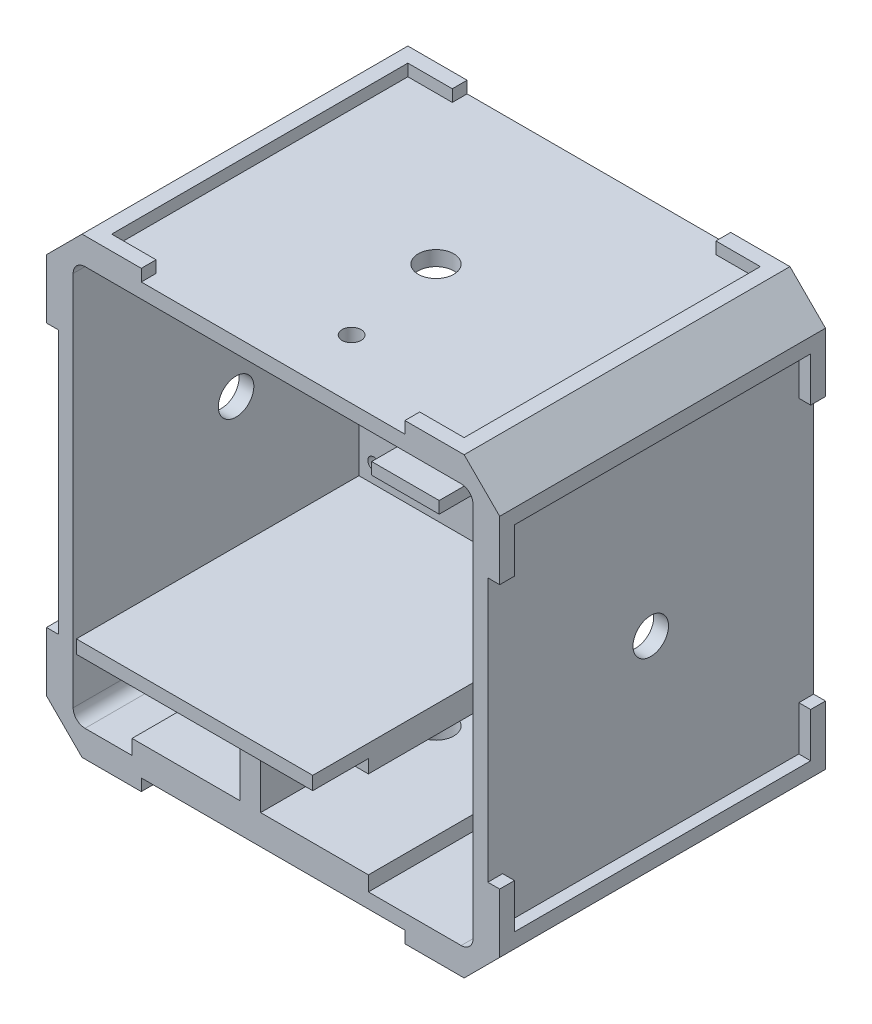
SolidWorks part; units mm, degrees
ref_plane "Front Plane" through (0, 0, 0) normal (0, 0, 1) x (1, 0, 0)
ref_plane "Top Plane" through (0, 0, 0) normal (0, 1, 0) x (1, 0, 0)
ref_plane "Right Plane" through (0, 0, 0) normal (1, 0, 0) x (0, 0, -1)
sketch "Sketch1" plane through (0, 0, 0) normal (0, 0, 1) x (1, 0, 0)
  line L0 (-33.75, -33.75) -> (33.75, -33.75) construction
  line L1 (-31.75, 33.75) -> (31.75, 33.75)
  line L2 (-33.75, 31.75) -> (-33.75, -31.75)
  line L3 (-31.75, -33.75) -> (31.75, -33.75)
  line L4 (33.75, 31.75) -> (33.75, -31.75)
  line L5 (-36.25, 32.25) -> (-36.25, -32.25)
  line L6 (33.75, 33.75) -> (33.75, -33.75) construction
  line L7 (-32.25, -36.25) -> (32.25, -36.25)
  line L8 (36.25, 32.25) -> (36.25, -32.25)
  line L9 (-32.25, 36.25) -> (32.25, 36.25)
  line L10 (-36.25, 36.25) -> (-36.25, -36.25) construction
  line L11 (-36.25, 36.25) -> (36.25, 36.25) construction
  line L12 (-33.75, 33.75) -> (33.75, 33.75) construction
  line L13 (-33.75, 33.75) -> (-33.75, -33.75) construction
  line L14 (-36.25, -36.25) -> (36.25, -36.25) construction
  line L15 (36.25, 36.25) -> (36.25, -36.25) construction
  line L16 (55, 0) -> (-55, 0) construction
  line L17 (0, -55) -> (0, 55) construction
  arc A0 (-36.25, 32.25) -> (-32.25, 36.25) centre (-32.25, 32.25) cw
  arc A1 (-31.75, 33.75) -> (-33.75, 31.75) centre (-31.75, 31.75) ccw
  arc A2 (-33.75, -31.75) -> (-31.75, -33.75) centre (-31.75, -31.75) ccw
  arc A3 (31.75, -33.75) -> (33.75, -31.75) centre (31.75, -31.75) ccw
  arc A4 (31.75, 33.75) -> (33.75, 31.75) centre (31.75, 31.75) cw
  arc A5 (-36.25, -32.25) -> (-32.25, -36.25) centre (-32.25, -32.25) ccw
  arc A6 (32.25, -36.25) -> (36.25, -32.25) centre (32.25, -32.25) ccw
  arc A7 (36.25, 32.25) -> (32.25, 36.25) centre (32.25, 32.25) ccw
  point P36 (-33.75, 0)
  point P39 (0, 33.75)
  dimension "D3" = 4
  dimension "D4" = 2
  dimension "D5" = 2
  dimension "D6" = 4
  dimension "D1" = 67.5
  dimension "D2" = 2.5
extrude "Boss-Extrude1" add sketch "Sketch1" along normal blind 55
sketch "Sketch2" plane through (0, 0, 0) normal (0, 0, 1) x (1, 0, 0)
  line L1 (-33.75, 33.75) -> (33.75, 33.75)
  line L2 (-33.75, 33.75) -> (-33.75, -33.75)
  line L3 (-33.75, -33.75) -> (33.75, -33.75)
  line L4 (33.75, 33.75) -> (33.75, -33.75)
extrude "Boss-Extrude2" add sketch "Sketch2" along normal blind 2.5
sketch "Sketch3" plane through (0, 0, 2.5) normal (0, 0, 1) x (1, 0, 0)
  line L0 (-4.38, 17.29) -> (-18.88, 12.29) construction
  line L1 (-19.88, 11.29) -> (-3.38, 11.29)
  line L2 (-18.88, 12.29) -> (-4.38, 12.29) construction
  line L3 (-18.88, 12.29) -> (-18.88, 17.29) construction
  line L4 (-18.88, 17.29) -> (-4.38, 17.29) construction
  line L5 (-4.38, 12.29) -> (-4.38, 17.29) construction
  line L6 (-3.38, 11.29) -> (-3.38, 18.29)
  line L7 (-19.88, 18.29) -> (-3.38, 18.29)
  line L8 (-19.88, 11.29) -> (-19.88, 18.29)
  line L9 (-36.25, 32.25) -> (-36.25, -32.25) construction
  line L10 (-3, -7) -> (3, -7) construction
  line L11 (-3, -7) -> (-3, 7) construction
  line L12 (-3, 7) -> (3, 7) construction
  line L13 (3, -7) -> (3, 7) construction
  line L14 (-3, -7) -> (3, 7) construction
  line L15 (-3, 7) -> (3, -7) construction
  line L16 (32.25, 36.25) -> (-32.25, 36.25) construction
  line L17 (-4, -8) -> (-4, 8)
  line L18 (-4, 8) -> (4, 8)
  line L19 (4, -8) -> (4, 8)
  line L20 (-4, -8) -> (4, -8)
  line L21 (-18.88, 17.29) -> (-4.38, 12.29) construction
  point P0 (0, 0)
  dimension "D2" = 6
  dimension "D3" = 14
  dimension "D5" = 14.5
  dimension "D6" = 5
  dimension "D7" = 16.37
  dimension "D8" = 23.96
  dimension "D1" = 1
  dimension "D4" = 1
extrude "Cut-Extrude1" cut sketch "Sketch3" against normal up to next
fillet "Fillet1" radius 1 8 edges at (-19.88, 11.29, 1.25) (-19.88, 18.29, 1.25) (-3.38, 18.29, 1.25) (-3.38, 11.29, 1.25) (4, -8, 1.25) (-4, -8, 1.25) (-4, 8, 1.25) (4, 8, 1.25)
sketch "Sketch4" plane through (0, 0, 0) normal (0, 0, -1) x (-1, 0, 0)
  line L0 (-32.25, 36.25) -> (32.25, 36.25) construction
  line L1 (-36.25, -32.25) -> (-36.25, 32.25) construction
  circle A0 centre (-28.75, 28.75) radius 1.5
  dimension "D3" = 3
  dimension "D1" = 7.5
  dimension "D2" = 7.5
extrude "Cut-Extrude2" cut sketch "Sketch4" against normal up to next
mirror "Mirror1" about plane through (0, 0, 0) normal (1, 0, 0) of "Cut-Extrude2"
mirror "Mirror2" about plane through (0, 0, 0) normal (0, 1, 0) of "Mirror1"
sketch "Sketch5" plane through (0, 0, 0) normal (1, 0, 0) x (0, 0, -1)
  line L0 (-14.7, 14) -> (-64.4, 14)
  line L1 (-16.7, 12) -> (-62.4, 12)
  line L2 (-16.7, 12) -> (-16.7, -12)
  line L3 (-16.7, -12) -> (-62.4, -12)
  line L5 (-64.4, 14) -> (-64.4, 12)
  line L6 (-14.7, -14) -> (-64.4, -14)
  line L7 (-14.7, 14) -> (-14.7, -14)
  line L8 (-62.4, 12) -> (-64.4, 12)
  line L9 (-62.4, -12) -> (-64.4, -12)
  line L10 (-64.4, -12) -> (-64.4, -14)
  line L11 (-62.4, 12) -> (-62.4, -12) construction
  line L12 (-64.4, 14) -> (-64.4, -14) construction
  line L13 (30.25, 0) -> (-30.25, 0) construction
  line L14 (-55, 32.25) -> (-55, -32.25) construction
  dimension "D1" = 45.7
  dimension "D2" = 24
  dimension "D4" = 12
  dimension "D5" = 9.4
  dimension "D3" = 2
extrude "Boss-Extrude3" add sketch "Sketch5" along normal blind 16.09 and the other way blind 23.81 separate body
sketch "Sketch6" plane through (0, 0, 64.4) normal (0, 0, 1) x (1, 0, 0)
  line L0 (-23.81, -14) -> (16.09, -14) construction
  line L1 (-23.81, -14) -> (16.09, -14)
  line L2 (-23.81, -14) -> (-23.81, -16.5)
  line L3 (-23.81, -16.5) -> (-5.61, -16.5)
  line L4 (16.09, -14) -> (16.09, -16.5)
  line L5 (-31.75, -33.75) -> (31.75, -33.75) construction
  line L6 (-23.81, -33.75) -> (16.09, -33.75)
  line L7 (-23.81, -33.75) -> (-23.81, -31.25)
  line L8 (-23.81, -31.25) -> (-5.61, -31.25)
  line L9 (16.09, -33.75) -> (16.09, -31.25)
  line L10 (-2.11, -16.5) -> (16.09, -16.5)
  line L12 (-5.61, -16.5) -> (-5.61, -31.25)
  line L14 (-2.11, -16.5) -> (-2.11, -31.25)
  line L15 (-2.11, -31.25) -> (16.09, -31.25)
  line L16 (-23.81, -12) -> (-23.81, -14) construction
  dimension "D1" = 2.5
  dimension "D2" = 2.5
  dimension "D3" = 39.9
  dimension "D4" = 39.9
  dimension "D5" = 3.5
  dimension "D6" = 18.2
  dimension "D7" = 18.2
extrude "Boss-Extrude4" add sketch "Sketch6" against normal blind 47
sketch "Sketch7" plane through (0, 0, 64.4) normal (0, 0, 1) x (1, 0, 0)
  line L0 (-23.81, -12) -> (-23.81, -16.5) construction
  line L1 (-23.81, -14.25) -> (16.09, -14.25)
  line L2 (-23.81, -14.25) -> (-23.81, -33.75)
  line L3 (-23.81, -33.75) -> (16.09, -33.75)
  line L4 (16.09, -14.25) -> (16.09, -33.75)
  line L5 (16.09, -33.75) -> (31.75, -33.75) construction
  line L6 (16.09, -33.75) -> (16.09, -31.25) construction
extrude "Cut-Extrude3" cut sketch "Sketch7" against normal blind 9.4
sketch "Sketch8" plane through (-23.81, 0, 0) normal (-1, 0, 0) x (0, 0, 1)
  line L0 (16.7, 12) -> (16.7, -12) construction
  line L1 (16.7, 12) -> (22.2, 12)
  line L2 (16.7, 12) -> (16.7, 6.5)
  line L3 (16.7, 6.5) -> (20.6, 6.5)
  line L4 (22.2, 12) -> (22.2, 8.1)
  arc A0 (20.6, 6.5) -> (22.2, 8.1) centre (20.6, 8.1) ccw
  circle A1 centre (19.7, 9) radius 1 construction
  circle A2 centre (19.7, 9) radius 1.8
  dimension "D1" = 1.6
  dimension "D4" = 3.6
  dimension "D5" = 2
  dimension "D2" = 5.5
  dimension "D3" = 5.5
  dimension "D6" = 3
  dimension "D7" = 3
extrude "Boss-Extrude5" [suppressed] add sketch "Sketch8" against normal blind 3
sketch "Sketch9" [suppressed] plane through (-15.56, 0, 0) normal (-1, 0, 0) x (0, 0, 1)
  circle A0 centre (22.3967, 9) radius 1
  circle A1 centre (22.3967, 9) radius 2
  dimension "D1" = 2
  dimension "D2" = 1
extrude "Boss-Extrude6" [suppressed] add sketch "Sketch9" along normal blind 1.5
ref_plane "Plane1" through (-9.11, 0, 0) normal (-1, 0, 0) x (0, 0, 1)
mirror "Mirror3" [suppressed] about plane through (-9.11, 0, 0) normal (-1, 0, 0)
ref_plane "Plane2" through (0, 0, 0) normal (0, 1, 0) x (1, 0, 0)
mirror "Mirror4" [suppressed] about plane through (0, 0, 0) normal (0, 1, 0)
sketch "Sketch10" [suppressed] plane through (-36.25, 0, 0) normal (-1, 0, 0) x (0, 0, 1)
  circle A0 centre (22.3967, 9) radius 1.5
  circle A1 centre (22.3967, -9) radius 1.5
  dimension "D1" = 3
  dimension "D2" = 3
extrude "Cut-Extrude4" [suppressed] cut sketch "Sketch10" against normal through all
sketch "Sketch12" plane through (0, 36.25, 0) normal (0, 1, 0) x (1, 0, 0)
  line L0 (-32.25, -55) -> (-32.25, 0) construction
  line L1 (32.25, -55) -> (29.75, -55)
  line L2 (32.25, -55) -> (32.25, -45)
  line L3 (32.25, -45) -> (29.75, -45)
  line L4 (29.75, -52.5) -> (29.75, -45)
  line L5 (32.25, -55) -> (22.25, -55)
  line L6 (32.25, -55) -> (32.25, -52.5)
  line L7 (29.75, -52.5) -> (22.25, -52.5)
  line L8 (22.25, -55) -> (22.25, -52.5)
  line L10 (-32.25, 0) -> (-32.25, -10)
  line L11 (-32.25, -10) -> (-29.75, -10)
  line L12 (-29.75, -2.5) -> (-29.75, -10)
  line L13 (-32.25, 0) -> (-22.25, 0)
  line L15 (-29.75, -2.5) -> (-22.25, -2.5)
  line L16 (-22.25, 0) -> (-22.25, -2.5)
  line M6 (-32.25, -55) -> (32.25, -55)
  line M7 (32.25, -55) -> (32.25, 0)
  dimension "D1" = 2.5
  dimension "D2" = 10
  dimension "D3" = 2.5
  dimension "D4" = 10
  dimension "D5" = 2.5
extrude "Boss-Extrude7" add sketch "Sketch12" along normal blind 2 contours L8 L2 L3 L4 L7 M6 M7 | L10 L11 L12 L15 L16 L13 region at (31, 36.25, 54.8586)
sketch "Sketch13" plane through (0, 0, 0) normal (0, 0, -1) x (-1, 0, 0)
  line L3 (-33.75, 21.25) -> (-25.25, 21.25)
  line L4 (-21.25, 33.75) -> (-21.25, 25.25)
  line L6 (0, 35.42) -> (0, -35.42) construction
  line L8 (21.25, 33.75) -> (21.25, 25.25)
  line L9 (33.75, 21.25) -> (25.25, 21.25)
  line L12 (35.42, 0) -> (-35.42, 0) construction
  line L17 (33.75, -21.25) -> (25.25, -21.25)
  line L18 (21.25, -33.75) -> (21.25, -25.25)
  line L19 (-21.25, -33.75) -> (-21.25, -25.25)
  line L20 (-33.75, -21.25) -> (-25.25, -21.25)
  line L27 (-33.75, 21.25) -> (-33.75, -21.25)
  line L29 (33.75, 21.25) -> (33.75, -21.25)
  line L34 (-21.25, 33.75) -> (21.25, 33.75)
  line L36 (-21.25, -33.75) -> (21.25, -33.75)
  arc A2 (-25.25, 21.25) -> (-21.25, 25.25) centre (-25.25, 25.25) ccw
  arc A4 (25.25, 21.25) -> (21.25, 25.25) centre (25.25, 25.25) cw
  arc A7 (25.25, -21.25) -> (21.25, -25.25) centre (25.25, -25.25) ccw
  arc A8 (-25.25, -21.25) -> (-21.25, -25.25) centre (-25.25, -25.25) cw
  dimension "D3" = 4
extrude "Cut-Extrude6" cut sketch "Sketch13" against normal up to next and the other way through all
sketch "Sketch14" plane through (0, 0, 14.7) normal (0, 0, -1) x (-1, 0, 0)
  line L1 (23.81, 14) -> (9.11, 14)
  line L2 (23.81, 14) -> (23.81, 12)
  line L3 (23.81, 12) -> (9.11, 12)
  line L4 (9.11, 14) -> (9.11, 12)
  dimension "D1" = 14.7
  dimension "D2" = 2
extrude "Cut-Extrude7" cut sketch "Sketch14" against normal up to next
sketch "Sketch15" plane through (0, 36.25, 0) normal (0, 1, 0) x (1, 0, 0)
  line L0 (22.25, -55) -> (-32.25, -55) construction
  line L1 (33.75, -55) -> (33.75, -2.5) construction
  circle A0 centre (3.25, -45) radius 1.6
  dimension "D1" = 3.2
  dimension "D2" = 10
  dimension "D3" = 30.5
extrude "Cut-Extrude8" cut sketch "Sketch15" against normal up to surface (2.5 mm away) and the other way through all up to face at (0, 33.75, 15)
sketch "Sketch16" plane through (-33.75, 0, 0) normal (1, 0, 0) x (0, 0, -1)
  line L2 (-16, 32.15) -> (-16, 29.65)
  line L7 (-16, 29.65) -> (-8.5, 29.65)
  line L9 (-16, 32.15) -> (-8.5, 32.15)
  line L10 (-8.5, 29.65) -> (-8.5, 32.15)
  line L12 (0, -32.25) -> (0, 32.25) construction
  dimension "D1" = 7.5
  dimension "D3" = 16
extrude "Boss-Extrude8" add sketch "Sketch16" along normal blind 7
sketch "Sketch11" plane through (0, 14, 0) normal (0, 1, 0) x (1, 0, 0)
  line L0 (1.19, -39.55) -> (12.59, -39.55)
  line L1 (-23.81, -64.4) -> (1.19, -64.4)
  line L2 (-23.81, -64.4) -> (-23.81, -14.7)
  line L3 (-23.81, -14.7) -> (1.19, -14.7)
  line L4 (1.19, -39.55) -> (1.19, -14.7)
  line L5 (16.09, -64.4) -> (12.59, -64.4)
  line L6 (16.09, -64.4) -> (16.09, -14.7)
  line L7 (16.09, -14.7) -> (12.59, -14.7)
  line L8 (12.59, -39.55) -> (12.59, -14.7)
  line L9 (1.19, -64.4) -> (12.59, -64.4)
  dimension "D1" = 25
  dimension "D2" = 49.7
  dimension "D3" = 3.5
extrude "Cut-Extrude5" cut sketch "Sketch11" against normal blind 2
sketch "Sketch17" plane through (0, 0, 14.7) normal (0, 0, -1) x (-1, 0, 0)
  line L0 (-16.09, -14) -> (-16.09, 12) construction
  line L1 (-1.19, 12) -> (23.81, 12) construction
  line L2 (23.81, -14) -> (23.81, 12) construction
  circle A0 centre (-13.59, 9) radius 1
  circle A1 centre (-13.59, -9) radius 1
  circle A2 centre (21.31, -9) radius 1
  dimension "D1" = 2
  dimension "D2" = 2.5
  dimension "D3" = 3
  dimension "D4" = 2.5
  dimension "D6" = 18
extrude "Cut-Extrude9" cut sketch "Sketch17" against normal up to next
sketch "Sketch19" plane through (0, 36.25, 0) normal (0, 1, 0) x (1, 0, 0)
  line L0 (32.25, -55) -> (-32.25, 0) construction
  line L1 (-32.25, 0) -> (-22.25, 0) construction
  line L2 (32.25, 0) -> (-32.25, -55) construction
  line L3 (32.25, -45) -> (32.25, 0) construction
  line L4 (32.25, 0) -> (-22.25, 0) construction
  line L5 (-32.25, 0) -> (-32.25, -10) construction
  line L6 (-32.25, 0) -> (-32.25, -10) construction
  circle A0 centre (0, -27.5) radius 3
  dimension "D1" = 6
extrude "Cut-Extrude10" cut sketch "Sketch19" against normal blind 2.5
sketch "Sketch20" plane through (36.25, 0, -36.25) normal (-1, 0, 0) x (0, 0, 1)
  line L0 (36.25, -32.25) -> (36.25, 32.25) construction
  line L1 (36.25, -32.25) -> (36.25, -22.25)
  line L2 (36.25, -32.25) -> (46.25, -32.25)
  line L3 (46.25, -32.25) -> (46.25, -29.75)
  line L4 (38.75, -29.75) -> (46.25, -29.75)
  line L5 (36.25, -32.25) -> (36.25, -22.25)
  line L7 (38.75, -29.75) -> (38.75, -22.25)
  line L8 (36.25, -22.25) -> (38.75, -22.25)
  line L10 (91.25, 32.25) -> (81.25, 32.25)
  line L11 (81.25, 32.25) -> (81.25, 29.75)
  line L12 (88.75, 29.75) -> (81.25, 29.75)
  line L13 (91.25, 32.25) -> (91.25, 22.25)
  line L15 (88.75, 29.75) -> (88.75, 22.25)
  line L16 (91.25, 22.25) -> (88.75, 22.25)
  line M25 (36.25, -32.25) -> (36.25, 32.25)
  line M26 (36.25, 32.25) -> (91.25, 32.25)
  line M27 (91.25, 32.25) -> (91.25, -32.25)
  line M28 (91.25, -32.25) -> (36.25, -32.25)
  dimension "D1" = 2.5
  dimension "D2" = 10
  dimension "D3" = 2.5
  dimension "D4" = 10
  dimension "D5" = 2.5
  dimension "D6" = 55
  dimension "D7" = 64.5
  dimension "D8" = 10
  dimension "D9" = 7.5
  dimension "D10" = 7.5
extrude "Boss-Extrude9" add sketch "Sketch20" against normal blind 2 contours L16 L15 L12 L11 M27 M26 | L8 L7 L4 L3 M25 M28 region at (36.25, -27.25, 0.1414) region at (36.25, 32.1086, 50)
ref_axis "Axis1" through (0, 0, 67.62) along (0, 0, -1)
pattern_circular "CirPattern1" count 4 every 90 about axis through (0, 0, 67.62) along (0, 0, -1) of "Boss-Extrude7", "Cut-Extrude10"
pattern_circular "CirPattern2" count 4 every 90 about axis through (0, 0, 67.62) along (0, 0, -1) of "Boss-Extrude9"
sketch "Sketch21" plane through (0, -33.75, 0) normal (0, -1, 0) x (1, 0, 0)
  line L0 (-2.11, 25.3674) -> (-2.11, 29.6326)
  arc A0 (-2.11, 25.3674) -> (-2.11, 29.6326) centre (0, 27.5) ccw
extrude "Cut-Extrude11" cut sketch "Sketch21" against normal blind 2.5
sketch "Sketch22" plane through (0, 0, 55) normal (0, 0, 1) x (1, 0, 0)
  line L0 (-38.25, 32.25) -> (-32.25, 38.25)
  line L1 (-32.25, 38.25) -> (-29.75, 38.25)
  line L8 (-29.75, 38.25) -> (-29.75, 33.75)
  line L13 (-38.25, 29.75) -> (-33.75, 29.75)
  line L20 (-38.25, 29.75) -> (-38.25, 32.25)
  line L24 (-32.25, 38.25) -> (-22.25, 38.25) construction
  line L26 (-33.75, 31.75) -> (-33.75, -31.75) construction
  line L27 (-38.25, 22.25) -> (-38.25, 32.25) construction
  line L28 (0, -35.42) -> (0, 35.42) construction
  line L29 (33.75, 33.75) -> (33.75, 29.75)
  line L30 (33.75, 33.75) -> (29.75, 33.75)
  line L31 (38.25, 29.75) -> (38.25, 32.25)
  line L32 (38.25, 29.75) -> (33.75, 29.75)
  line L33 (-33.75, 33.75) -> (-29.75, 33.75)
  line L34 (-33.75, 33.75) -> (-33.75, 29.75)
  line L37 (29.75, 38.25) -> (29.75, 33.75)
  line L38 (32.25, 38.25) -> (29.75, 38.25)
  line L39 (38.25, 32.25) -> (32.25, 38.25)
  line L40 (35.42, 0) -> (-35.42, 0) construction
  line L41 (38.25, -32.25) -> (32.25, -38.25)
  line L42 (32.25, -38.25) -> (29.75, -38.25)
  line L43 (29.75, -38.25) -> (29.75, -33.75)
  line L44 (-33.75, -33.75) -> (-33.75, -29.75)
  line L45 (-33.75, -33.75) -> (-29.75, -33.75)
  line L46 (38.25, -29.75) -> (33.75, -29.75)
  line L47 (38.25, -29.75) -> (38.25, -32.25)
  line L48 (33.75, -33.75) -> (29.75, -33.75)
  line L49 (33.75, -33.75) -> (33.75, -29.75)
  line L50 (-38.25, -29.75) -> (-38.25, -32.25)
  line L51 (-38.25, -29.75) -> (-33.75, -29.75)
  line L52 (-29.75, -38.25) -> (-29.75, -33.75)
  line L53 (-32.25, -38.25) -> (-29.75, -38.25)
  line L54 (-38.25, -32.25) -> (-32.25, -38.25)
  point P5 (-33.75, 29.75)
  point P11 (-39.1756, 29.9277)
  point P13 (-38.25, 29.75)
  point P32 (-22.25, 38.25)
  point P33 (-30.6931, 38.25)
  point P36 (0, 0)
  point P37 (0, 0)
  dimension "D1" = 2.5
  dimension "D2" = 2.5
extrude "Boss-Extrude12" add sketch "Sketch22" against normal through all
